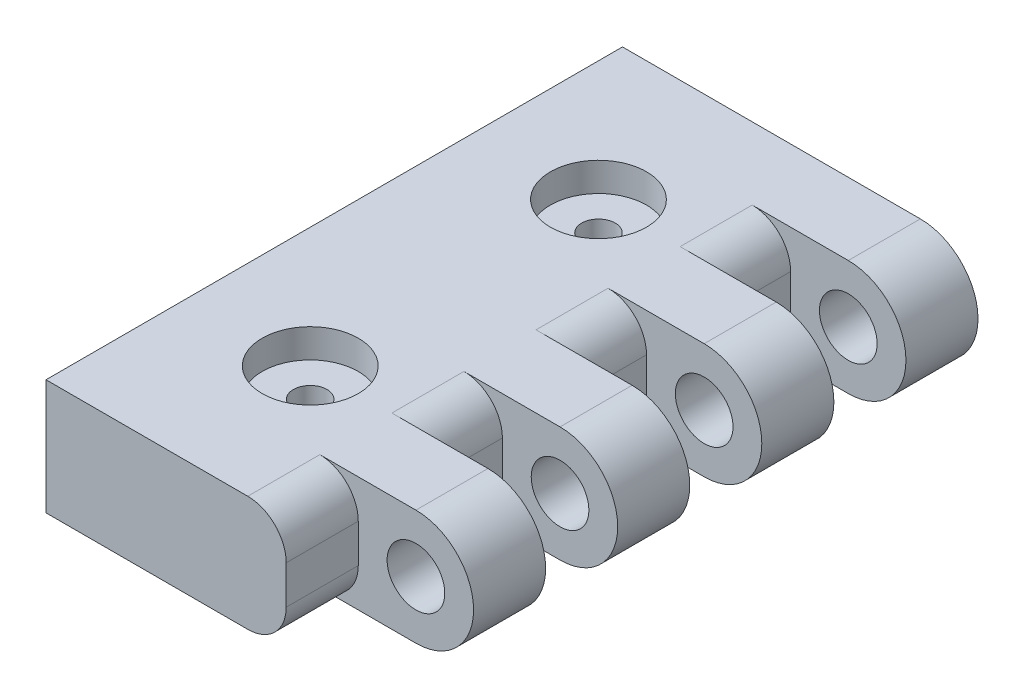
SolidWorks part; units mm, degrees
ref_plane "Front" through (0, 0, 0) normal (0, 0, 1) x (1, 0, 0)
ref_plane "Top" through (0, 0, 0) normal (0, 1, 0) x (1, 0, 0)
ref_plane "Right" through (0, 0, 0) normal (1, 0, 0) x (0, 0, -1)
sketch "Sketch1" plane through (0, 0, 0) normal (0, 1, 0) x (1, 0, 0)
  line L1 (0, 0) -> (-25, 0)
  line L2 (0, 0) -> (0, 60)
  line L3 (0, 60) -> (-25, 60)
  line L4 (-25, 0) -> (-25, 60)
  dimension "D1" = 60
  dimension "D2" = 25
extrude "Boss-Extrude1" add sketch "Sketch1" along normal blind 12
sketch "Sketch2" plane through (0, 0, 0) normal (0, 0, 1) x (1, 0, 0)
  line L0 (0, 0) -> (13.9056, 0) construction
  line L1 (0, 12) -> (0, 0) construction
  line L2 (0, 6) -> (0, 0)
  line L3 (0, 0) -> (6, 0)
  line L4 (0, 6) -> (0, 12)
  line L5 (0, 12) -> (6, 12)
  arc A0 (6, 0) -> (6, 12) centre (6, 6) ccw
  circle A1 centre (6, 6) radius 3
  dimension "D1" = 12
  dimension "D2" = 6
extrude "Boss-Extrude2" add sketch "Sketch2" against normal up to surface (60 mm away) up to face at (-12.5, 6, -60)
sketch "Sketch3" plane through (0, 12, 0) normal (0, 1, 0) x (1, 0, 0)
  line L1 (0, 52.5) -> (12, 52.5)
  line L2 (0, 52.5) -> (0, 45)
  line L3 (0, 45) -> (12, 45)
  line L4 (12, 52.5) -> (12, 45)
  line L5 (12, 0) -> (12, 60) construction
  line L6 (6, 60) -> (-25, 60) construction
  dimension "D1" = 12
  dimension "D2" = 7.5
  dimension "7.5" = 7.5
extrude "Cut-Extrude1" cut sketch "Sketch3" against normal through all
pattern_linear "LPattern1" count 4 spacing 15 along (0, 0, 1) of "Cut-Extrude1"
sketch "Sketch4" plane through (0, 12, 0) normal (0, 1, 0) x (1, 0, 0)
  line L1 (6, 60) -> (-25, 60) construction
  line L2 (-25, 0) -> (0, 0) construction
  line L3 (-12.5, 0) -> (-12.5, 45) construction
  circle A0 centre (-12.5, 45) radius 1.75
  circle A1 centre (-12.5, 15) radius 1.75
  dimension "D4" = 3.5
  dimension "D2" = 15
  dimension "D3" = 15
extrude "Cut-Extrude2" cut sketch "Sketch4" against normal through all
sketch "Sketch5" plane through (0, 12, 0) normal (0, 1, 0) x (1, 0, 0)
  circle A0 centre (-12.5, 45) radius 5
  circle A1 centre (-12.5, 15) radius 5
  dimension "D1" = 10
extrude "Cut-Extrude3" cut sketch "Sketch5" against normal blind 3
pattern_linear "LPattern2" count 2 spacing 9 along (0, -1, 0) of "Cut-Extrude3"
fillet "Fillet1" radius 4 8 edges at (0, 0, -3.75) (0, 12, -3.75) (0, 0, -18.75) (0, 12, -18.75) (0, 0, -33.75) (0, 12, -33.75) (0, 0, -48.75) (0, 12, -48.75)
